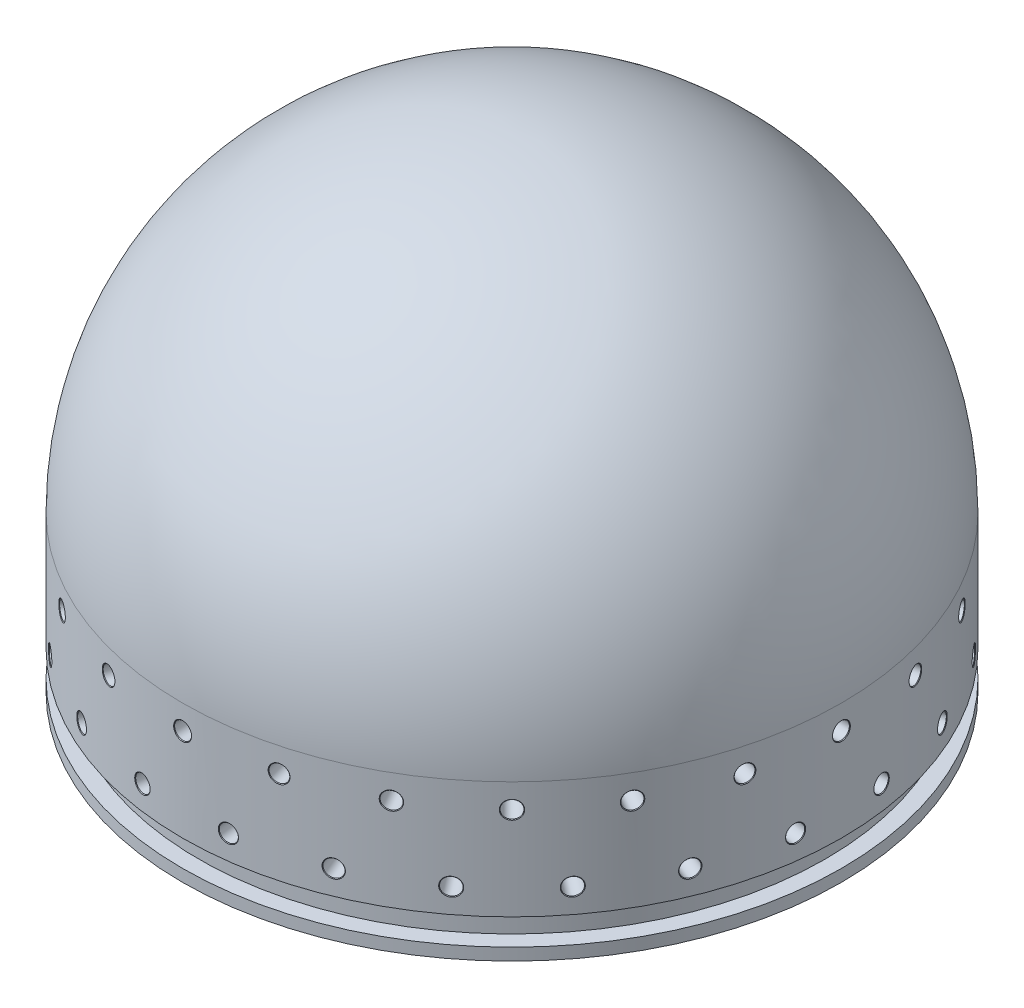
SolidWorks part; units mm, degrees
material "AW-6082-T6 (PA4)"
ref_plane "Płaszczyzna przednia" through (0, 0, 0) normal (0, 0, 1) x (1, 0, 0)
ref_plane "Płaszczyzna górna" through (0, 0, 0) normal (0, 1, 0) x (1, 0, 0)
ref_plane "Płaszczyzna prawa" through (0, 0, 0) normal (1, 0, 0) x (0, 0, -1)
sketch "Szkic1" plane through (0, 0, 0) normal (0, 1, 0) x (1, 0, 0)
  circle A0 centre (0, 0) radius 81.7
  dimension "D1" = 163.4
extrude "Dodanie-wyciągnięcie1" add sketch "Szkic1" along normal blind 38.5
ref_plane "Płaszczyzna1" through (0, 0, -81.7) normal (0, 0, -1) x (-1, 0, 0)
ref_plane "Płaszczyzna2" through (10.664, 0, -81.001) normal (0.1305, 0, -0.9914) x (0, -1, 0)
hole_wizard "Otwór gwintowany M51" positions "Szkic2" profile "Szkic3" hole size "M5" standard "ISO"
sketch "Szkic2" plane through (0, 0, -81.7) normal (0, 0, -1) x (-1, 0, 0)
  line L0 (81.7, 0) -> (81.7, 38.5) construction
  line L1 (-81.7, 38.5) -> (-81.7, 0) construction
  line L2 (81.7, 0) -> (81.7, 38.5)
  line L3 (-81.7, 38.5) -> (-81.7, 0)
  line L4 (0, 51.4702) -> (0, -13.4001) construction
  line L5 (81.7, 38.5) -> (-81.7, 38.5) construction
  point P11 (0, 32.5)
  dimension "D1" = 6
sketch "Szkic3" plane through (0, 32.5, -81.7) normal (1, 0, 0) x (0, 1, 0)
  line L0 (0, 0) -> (0, 9.2618)
  line L1 (0, 9.2618) -> (2.1, 8)
  line L2 (2.1, 8) -> (2.1, 0.15)
  line L3 (2.1, 0.15) -> (2.25, 0)
  line L5 (2.25, 0) -> (0, 0)
  line L6 (-2.1, 0.15) -> (-2.25, 0) construction
  line L10 (0, 9.2618) -> (-2.1, 8) construction
  line L11 (0, -6.35) -> (0, 107.95) construction
  dimension "Średnica otworu" = 4.2
  dimension "Głębokośc otworu" = 8
  dimension "Średnica zewnętrznego pogłębienia stożkowego" = 4.5
  dimension "Kąt zewnętrznego pogłębienia stożkowego" = 90
  dimension "Kąt wiertła" = 118
hole_wizard "Otwór gwintowany M52" positions "Szkic6" profile "Szkic7" hole size "M5" standard "ISO"
sketch "Szkic6" plane through (10.664, 0, -81.001) normal (0.1305, 0, -0.9914) x (0, -1, 0)
  line L0 (-38.5, -81.7) -> (0, -81.7) construction
  line L1 (0, 81.7) -> (-38.5, 81.7) construction
  line L2 (-38.5, -81.7) -> (0, -81.7)
  line L3 (0, 81.7) -> (-38.5, 81.7)
  line L4 (-54.6249, 0) -> (16.9218, 0) construction
  ellipse E0 centre (-32.5, 10.6444) end of major axis (-30.4, 10.6444) minor radius 2.082 construction
  point P10 (-15.5, 0)
  dimension "D1" = 17
sketch "Szkic7" plane through (10.664, 15.5, -81.001) normal (0, 1, 0) x (-0.9914, 0, -0.1305)
  line L0 (0, 0) -> (0, 9.2618)
  line L1 (0, 9.2618) -> (2.1, 8)
  line L2 (2.1, 8) -> (2.1, 0.15)
  line L3 (2.1, 0.15) -> (2.25, 0)
  line L5 (2.25, 0) -> (0, 0)
  line L6 (-2.1, 0.15) -> (-2.25, 0) construction
  line L10 (0, 9.2618) -> (-2.1, 8) construction
  line L11 (0, -6.35) -> (0, 107.95) construction
  dimension "Średnica otworu" = 4.2
  dimension "Głębokośc otworu" = 8
  dimension "Średnica zewnętrznego pogłębienia stożkowego" = 4.5
  dimension "Kąt zewnętrznego pogłębienia stożkowego" = 90
  dimension "Kąt wiertła" = 118
pattern_circular "Szyk kołowy1" count 24 over 360 about axis through (0, 38.5, 0) along (0, -1, 0) of "Otwór gwintowany M51", "Otwór gwintowany M52"
sketch "Szkic8" plane through (0, 0, 0) normal (0, 0, 1) x (1, 0, 0)
  line L0 (-81.7, 30.25) -> (-81.7, 0) construction
  line L1 (-81.7, 30.25) -> (-81.7, 0)
  line L2 (-81.7, 0) -> (81.7, 0) construction
  line L3 (-81.7, 9.5) -> (-77.7, 9.5)
  line L4 (-81.7, 9.5) -> (-81.7, 3)
  line L5 (-81.7, 3) -> (-77.7, 3)
  line L6 (-77.7, 9.5) -> (-77.7, 3)
  line L8 (0, 56.0732) -> (0, -20.5484) construction
  line L9 (81.7, 0) -> (81.7, 30.25) construction
  dimension "D1" = 4
  dimension "D2" = 6.5
  dimension "D3" = 3
revolve "Wycięcie-obrót1" cut sketch "Szkic8" angle 360 about L8 region at (-79.7, 6.25, 0)
sketch "Szkic9" plane through (0, 0, 0) normal (0, 0, 1) x (1, 0, 0)
  line L0 (0, -10.2266) -> (0, 51.1756) construction
  line L1 (-81.7, 0) -> (81.7, 0) construction
  line L2 (0, 0) -> (-66.7, 0)
  line L3 (0, 0) -> (0, 23.5)
  line L4 (0, 23.5) -> (-66.7, 23.5)
  line L5 (-66.7, 0) -> (-66.7, 23.5)
  line L6 (-81.7, 30.2501) -> (-81.7, 9.5) construction
  line L7 (-81.7, 30.2501) -> (-81.7, 9.5)
  line L8 (-73.7, 34.6) -> (-73.7, 30.4) construction
  line L9 (81.7, 38.5) -> (-81.7, 38.5) construction
  line L10 (81.7, 38.5) -> (-81.7, 38.5)
  dimension "D1" = 15
  dimension "D2" = 7
  dimension "D3" = 15
revolve "Wycięcie-obrót2" cut sketch "Szkic9" angle 360 about L0 region at (-33.35, 11.75, 0)
sketch "Szkic10" plane through (0, 23.5, 0) normal (0, -1, 0) x (1, 0, 0)
  circle A1 centre (0, 0) radius 66.7
  circle A2 centre (0, 0) radius 66.7
  dimension "D1" = 0
extrude "Wytnij-wyciągnięcie1" cut sketch "Szkic10" against normal through all
sketch "Szkic11" plane through (0, 0, 0) normal (0, 0, 1) x (1, 0, 0)
  line L0 (0, 38.5) -> (0, 112.2) construction
  line L2 (0, 38.5) -> (-66.7, 38.5) construction
  line L4 (66.7, 38.5) -> (81.7, 38.5)
  line L6 (0, 120.2) -> (0, 112.2)
  line L7 (66.7, 38.5) -> (66.7, 48.5)
  line L8 (66.7, 38.5) -> (66.7, 12.7552) construction
  line L9 (66.7, 0) -> (66.7, 38.5) construction
  arc A0 (81.7, 38.5) -> (0, 120.2) centre (0, 38.5) ccw
  arc A3 (0, 112.2) -> (66.7, 48.5) centre (0, 45.4294) cw
  point P2 (0, 0)
  point P3 (66.7, 53.3511)
  point P14 (0, 44.9824)
  dimension "D2" = 10
  dimension "D1" = 8
revolve "Obrót3" add sketch "Szkic11" angle 360 about L0
